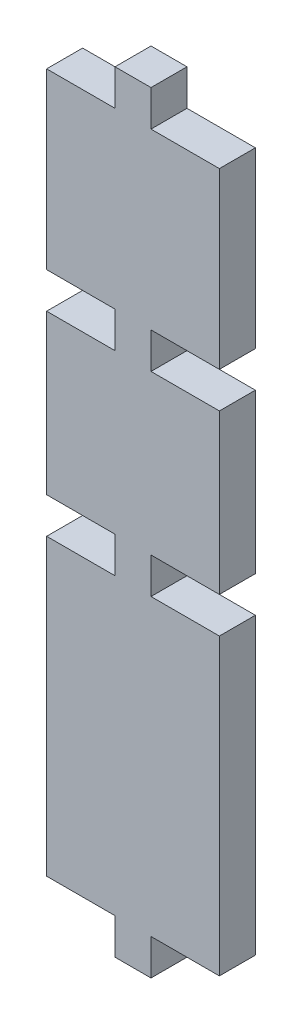
SolidWorks part; units mm, degrees
ref_plane "Front Plane" through (0, 0, 0) normal (0, 0, 1) x (1, 0, 0)
ref_plane "Top Plane" through (0, 0, 0) normal (0, 1, 0) x (1, 0, 0)
ref_plane "Right Plane" through (0, 0, 0) normal (1, 0, 0) x (0, 0, -1)
sketch "Sketch1" plane through (0, 0, 0) normal (0, 0, 1) x (1, 0, 0)
  line L0 (4.2711, -1.524) -> (4.2711, 0)
  line L1 (4.2711, -1.524) -> (1.3744, -1.524)
  line L2 (1.3744, -1.524) -> (1.3744, -13.9935)
  line L3 (4.2711, 0) -> (1.3744, 0)
  line L4 (1.3744, 0) -> (1.3744, 6.7327)
  line L5 (4.2711, 8.2567) -> (4.2711, 6.7327)
  line L6 (4.2711, 6.7327) -> (1.3744, 6.7327)
  line L7 (4.2711, 8.2567) -> (1.3744, 8.2567)
  line L8 (1.3744, 8.2567) -> (1.3744, 15.6227)
  line L9 (5.0331, 0) -> (5.0331, 6.7327) construction
  line L10 (5.7951, 0) -> (4.2711, 0) construction
  line L11 (5.7951, 6.7327) -> (4.2711, 6.7327) construction
  line L12 (8.6919, -1.524) -> (8.6919, -13.9935)
  line L13 (5.7951, 0) -> (8.6919, 0)
  line L14 (5.7951, -1.524) -> (8.6919, -1.524)
  line L15 (5.7951, -1.524) -> (5.7951, 0)
  line L16 (8.6919, 8.2567) -> (8.6919, 15.6227)
  line L17 (5.7951, 8.2567) -> (8.6919, 8.2567)
  line L18 (5.7951, 6.7327) -> (8.6919, 6.7327)
  line L19 (5.7951, 8.2567) -> (5.7951, 6.7327)
  line L20 (8.6919, 0) -> (8.6919, 6.7327)
  line L21 (1.3744, -13.9935) -> (4.2711, -13.9935)
  line L22 (8.6919, 15.6227) -> (5.7951, 15.6227)
  line L23 (5.0331, 15.6227) -> (5.0331, 17.1467) construction
  line L24 (5.0331, -13.9935) -> (5.0331, -15.5175) construction
  line L25 (4.2711, -13.9935) -> (4.2711, -15.5175)
  line L26 (5.7951, 15.6227) -> (5.7951, 17.1467)
  line L27 (5.7951, -13.9935) -> (5.7951, -15.5175)
  line L28 (4.2711, 15.6227) -> (4.2711, 17.1467)
  line L30 (4.2711, -15.5175) -> (5.7951, -15.5175)
  line L31 (4.2711, 15.6227) -> (1.3744, 15.6227)
  line L32 (5.7951, 17.1467) -> (4.2711, 17.1467)
  line L33 (5.7951, -13.9935) -> (8.6919, -13.9935)
extrude "Boss-Extrude1" add sketch "Sketch1" along normal blind 1.524
